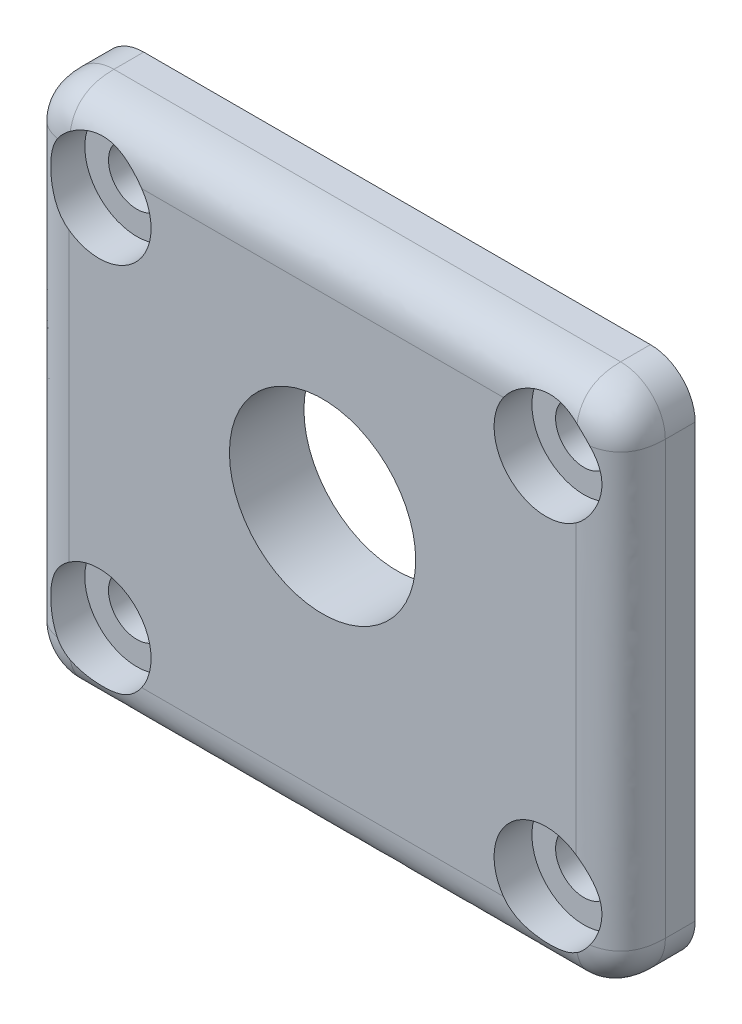
SolidWorks part; units mm, degrees
material "PA Type 6"
ref_plane "Front Plane" through (0, 0, 0) normal (0, 0, 1) x (1, 0, 0)
ref_plane "Top Plane" through (0, 0, 0) normal (0, 1, 0) x (1, 0, 0)
ref_plane "Right Plane" through (0, 0, 0) normal (1, 0, 0) x (0, 0, -1)
sketch "Sketch1" plane through (0, 0, 0) normal (0, 0, 1) x (1, 0, 0)
  line L1 (-20, 17.5) -> (20, 17.5)
  line L2 (-20, 17.5) -> (-20, -17.5)
  line L3 (-20, -17.5) -> (20, -17.5)
  line L4 (20, 17.5) -> (20, -17.5)
  line L5 (-20, 17.5) -> (20, -17.5) construction
  line L6 (-20, -17.5) -> (20, 17.5) construction
  point P0 (0, 0)
  dimension "D1" = 40
  dimension "D2" = 35
extrude "Boss-Extrude1" add sketch "Sketch1" along normal blind 5
sketch "Sketch2" plane through (0, 0, 5) normal (0, 0, 1) x (1, 0, 0)
  line L0 (20, 17.5) -> (-20, 17.5) construction
  line L1 (-20, 17.5) -> (-20, -17.5) construction
  line L2 (0, 17.5) -> (0, -17.5) construction
  line L3 (-20, -17.5) -> (20, -17.5) construction
  line L4 (20, 0) -> (-20, 0) construction
  line L5 (20, -17.5) -> (20, 17.5) construction
  circle A0 centre (-15, 12.5) radius 1.905
  circle A1 centre (15, 12.5) radius 1.905
  circle A2 centre (15, -12.5) radius 1.905
  circle A3 centre (-15, -12.5) radius 1.905
  dimension "D1" = 3.81
  dimension "D2" = 5
  dimension "D3" = 5
extrude "Cut-Extrude1" cut sketch "Sketch2" against normal through all
fillet "Fillet1" radius 3 4 edges at (20, 17.5, 2.5) (20, -17.5, 2.5) (-20, -17.5, 2.5) (-20, 17.5, 2.5)
sketch "Sketch3" plane through (0, 0, 5) normal (0, 0, 1) x (1, 0, 0)
  line L0 (0, 17.5) -> (0, -17.5) construction
  line L1 (17, 17.5) -> (-17, 17.5) construction
  line L2 (-17, -17.5) -> (17, -17.5) construction
  line L3 (-20, 0) -> (20, 0) construction
  line L4 (-20, 14.5) -> (-20, -14.5) construction
  line L5 (20, -14.5) -> (20, 14.5) construction
  circle A0 centre (-15, 12.5) radius 3.4925
  circle A1 centre (15, 12.5) radius 3.4925
  circle A2 centre (15, -12.5) radius 3.4925
  circle A3 centre (-15, -12.5) radius 3.4925
  dimension "D1" = 6.985
extrude "Cut-Extrude2" cut sketch "Sketch3" against normal blind 2.54
fillet "Fillet2" radius 3 4 edges at (20, 0, 5) (0, 17.5, 5) (0, -17.5, 5) (-20, 0, 5)
sketch "Sketch5" plane through (0, 0, 0) normal (0, 0, -1) x (-1, 0, 0)
  line L0 (0, 17.5) -> (0, -17.5) construction
  line L1 (-17, 17.5) -> (17, 17.5) construction
  line L2 (17, -17.5) -> (-17, -17.5) construction
  line L3 (-20, 0) -> (20, 0) construction
  line L4 (-20, -14.5) -> (-20, 14.5) construction
  line L5 (20, 14.5) -> (20, -14.5) construction
  line L6 (-9.601, -11) -> (9.601, -11)
  line L7 (13.5, 7.101) -> (13.5, -7.101)
  line L8 (13.5, 0) -> (13.5, -17.5) construction
  line L9 (-9.601, 11) -> (9.601, 11)
  line L10 (-13.5, 7.101) -> (-13.5, -7.101)
  line L11 (-10.5, 12) -> (10.5, 12)
  line L12 (14.5, 8) -> (14.5, -8)
  line L13 (-10.5, -12) -> (10.5, -12)
  line L14 (-14.5, 8) -> (-14.5, -8)
  arc A0 (13.5, -7.101) -> (9.601, -11) centre (14.5, -12) ccw
  arc A1 (13.5, 7.101) -> (9.601, 11) centre (14.5, 12) cw
  arc A2 (-13.5, -7.101) -> (-9.601, -11) centre (-14.5, -12) cw
  arc A3 (-13.5, 7.101) -> (-9.601, 11) centre (-14.5, 12) ccw
  arc A4 (14.5, 8) -> (10.5, 12) centre (14.5, 12) cw
  arc A5 (14.5, -8) -> (10.5, -12) centre (14.5, -12) ccw
  arc A6 (-14.5, -8) -> (-10.5, -12) centre (-14.5, -12) cw
  arc A7 (-14.5, 8) -> (-10.5, 12) centre (-14.5, 12) ccw
  arc A8 (13.5, -7.101) -> (9.601, -11) centre (14.5, -12) ccw construction
  point P24 (0, -11)
  point P29 (0, 11)
  dimension "D3" = 5.5
  dimension "D4" = 5
  dimension "D1" = 6.5
  dimension "D2" = 6.5
extrude "Boss-Extrude2" add sketch "Sketch5" along normal blind 2.5
sketch "Sketch6" plane through (0, 0, 0) normal (0, 0, -1) x (-1, 0, 0)
  line L5 (-13.25, -8) -> (13.25, -8)
  line L10 (13.25, -8) -> (13.25, -6)
  line L11 (-13.25, -6) -> (13.25, -6)
  line L13 (-13.25, -8) -> (-13.25, -6)
  line L14 (17, -17.5) -> (-17, -17.5) construction
  line L15 (0, 17.5) -> (0, -17.5) construction
  line L16 (-17, 17.5) -> (17, 17.5) construction
  point P9 (0, -6)
  dimension "D1" = 2
  dimension "D2" = 9.5
  dimension "D3" = 26.5
extrude "Cut-Extrude4" cut sketch "Sketch6" along normal up to next
sketch "Sketch7" plane through (0, 0, 5) normal (0, 0, 1) x (1, 0, 0)
  line L0 (17, -17.5) -> (-17, -17.5) construction
  circle A0 centre (0, 2.1) radius 6.25
  dimension "D2" = 12.5
  dimension "D1" = 19.6
extrude "Cut-Extrude3" cut sketch "Sketch7" against normal up to next
sketch "Sketch8" plane through (0, 0, 0) normal (0, 0, -1) x (-1, 0, 0)
  line L0 (-14.5, -8) -> (14.5, -8)
  line L8 (10.5, -12) -> (-10.5, -12)
  line L9 (10.5, -12) -> (-10.5, -12)
  arc A12 (14.5, -8) -> (10.5, -12) centre (14.5, -12) ccw
  arc A13 (-10.5, -12) -> (-14.5, -8) centre (-14.5, -12) ccw
  arc A14 (14.5, -8) -> (10.5, -12) centre (14.5, -12) ccw
  arc A15 (-10.5, -12) -> (-14.5, -8) centre (-14.5, -12) ccw
  dimension "D1" = 0
extrude "Boss-Extrude4" add sketch "Sketch8" along normal up to surface (2.5 mm away) up to face at (0, 0, -2.5)
